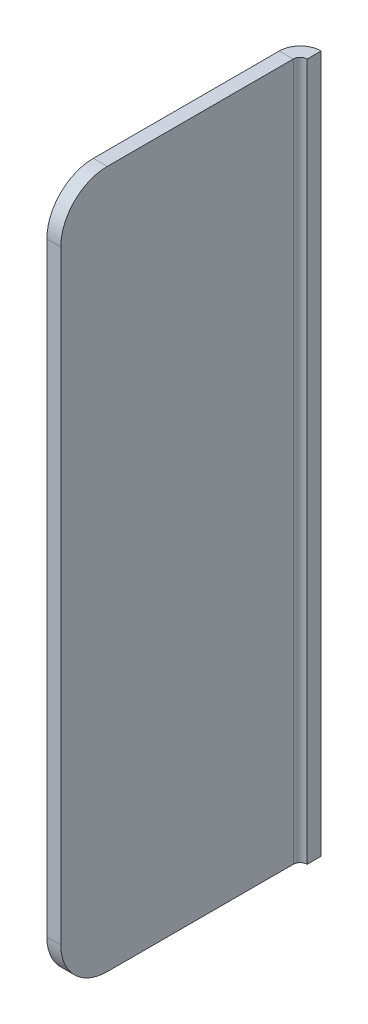
SolidWorks part; units mm, degrees
ref_plane "前视基准面" through (0, 0, 0) normal (0, 0, 1) x (1, 0, 0)
ref_plane "上视基准面" through (0, 0, 0) normal (0, 1, 0) x (1, 0, 0)
ref_plane "右视基准面" through (0, 0, 0) normal (1, 0, 0) x (0, 0, -1)
other "Configuration Table"
sketch "草图2" plane through (0, 0, 0) normal (0, 1, 0) x (1, 0, 0)
  line L0 (0, 0) -> (0, 100)
  arc A0 (0, 100) -> (6, 106) centre (6, 100) cw
  dimension "D2" = 6
  dimension "D1" = 100
sketch "草图3" plane through (0, 0, 0) normal (0, 0, 1) x (1, 0, 0)
  line L1 (-3, -150) -> (3, -150)
  line L2 (-3, -150) -> (-3, 150)
  line L3 (-3, 150) -> (3, 150)
  line L4 (3, -150) -> (3, 150)
  line L5 (-3, -150) -> (3, 150) construction
  line L6 (-3, 150) -> (3, -150) construction
  point P0 (0, 0)
  dimension "D1" = 6
  dimension "D2" = 300
sweep "扫描1" add profiles "草图3" path "草图2"
fillet "圆角1" radius 20 2 edges at (0, -150, 0) (0, 150, 0)
